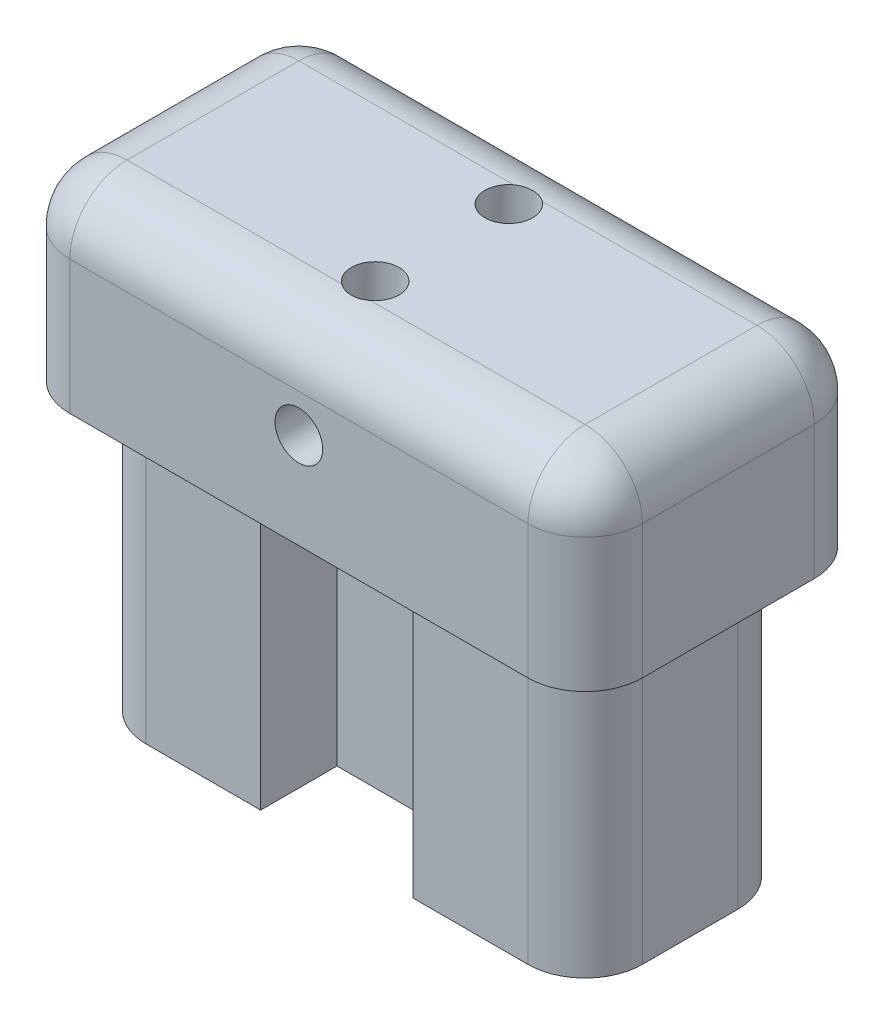
SolidWorks part; units mm, degrees
ref_plane "Front Plane" through (0, 0, 0) normal (0, 0, 1) x (1, 0, 0)
ref_plane "Top Plane" through (0, 0, 0) normal (0, 1, 0) x (1, 0, 0)
ref_plane "Right Plane" through (0, 0, 0) normal (1, 0, 0) x (0, 0, -1)
sketch "Sketch1" plane through (0, 0, 0) normal (0, 1, 0) x (1, 0, 0)
  line L1 (-15, -7.5) -> (15, -7.5)
  line L2 (-15, -7.5) -> (-15, 7.5)
  line L3 (-15, 7.5) -> (15, 7.5)
  line L4 (15, -7.5) -> (15, 7.5)
  line L5 (-15, -7.5) -> (15, 7.5) construction
  line L6 (-15, 7.5) -> (15, -7.5) construction
  point P0 (0, 0)
  dimension "D1" = 30
  dimension "D2" = 15
extrude "Boss-Extrude1" add sketch "Sketch1" along normal blind 10
sketch "Sketch2" plane through (0, 0, 0) normal (0, -1, 0) x (1, 0, 0)
  line L0 (15, 7.5) -> (15, -7.5) construction
  line L1 (-13, -5.5) -> (-4, -5.5)
  line L2 (-13, -5.5) -> (-13, 5.5)
  line L3 (-13, 5.5) -> (-4, 5.5)
  line L4 (13, -5.5) -> (13, 5.5)
  line L5 (-13, -5.5) -> (13, 5.5) construction
  line L6 (-13, 5.5) -> (13, -5.5) construction
  line L7 (-15, 7.5) -> (15, 7.5) construction
  line L8 (-4, 5.5) -> (-4, 1.5)
  line L9 (-4, 1.5) -> (3.9884, 1.5)
  line L10 (3.9884, 1.5) -> (3.9884, 5.5)
  line L11 (3.9884, 5.5) -> (13, 5.5)
  line L12 (-4, -5.5) -> (-4, -1.5)
  line L13 (-4, -1.5) -> (3.9884, -1.5)
  line L14 (3.9884, -1.5) -> (3.9884, -5.5)
  line L15 (3.9884, -5.5) -> (13, -5.5)
  point P0 (0, 0)
  dimension "D1" = 2
  dimension "D2" = 2
  dimension "D3" = 4
  dimension "D4" = 4
  dimension "D5" = 4
extrude "Boss-Extrude2" add sketch "Sketch2" along normal blind 15
fillet "Fillet1" radius 3 12 edges at (-15, 10, 0) (15, 10, 0) (0, 10, -7.5) (0, 10, 7.5) (15, 5, -7.5) (15, 5, 7.5) (-15, 5, -7.5) (-15, 5, 7.5) (13, -7.5, -5.5) (13, -7.5, 5.5) (-13, -7.5, -5.5) (-13, -7.5, 5.5)
sketch "Sketch3" plane through (0, 0, 0) normal (0, -1, 0) x (1, 0, 0)
  line L0 (-4, -1.5) -> (3.9884, -1.5) construction
  line L1 (3.9884, 1.5) -> (-4, 1.5) construction
  circle A0 centre (0, 3.5) radius 1.25
  circle A1 centre (0, -3.5) radius 1.25
  dimension "D1" = 2.5
  dimension "D2" = 2.5
  dimension "D3" = 2
  dimension "D4" = 2
extrude "Cut-Extrude1" cut sketch "Sketch3" against normal through all
sketch "Sketch4" plane through (0, 0, 7.5) normal (0, 0, 1) x (1, 0, 0)
  line L0 (-12, 0) -> (12, 0) construction
  circle A0 centre (0, 5) radius 1.25
  dimension "D1" = 2.5
  dimension "D2" = 5
extrude "Cut-Extrude2" cut sketch "Sketch4" against normal through all
